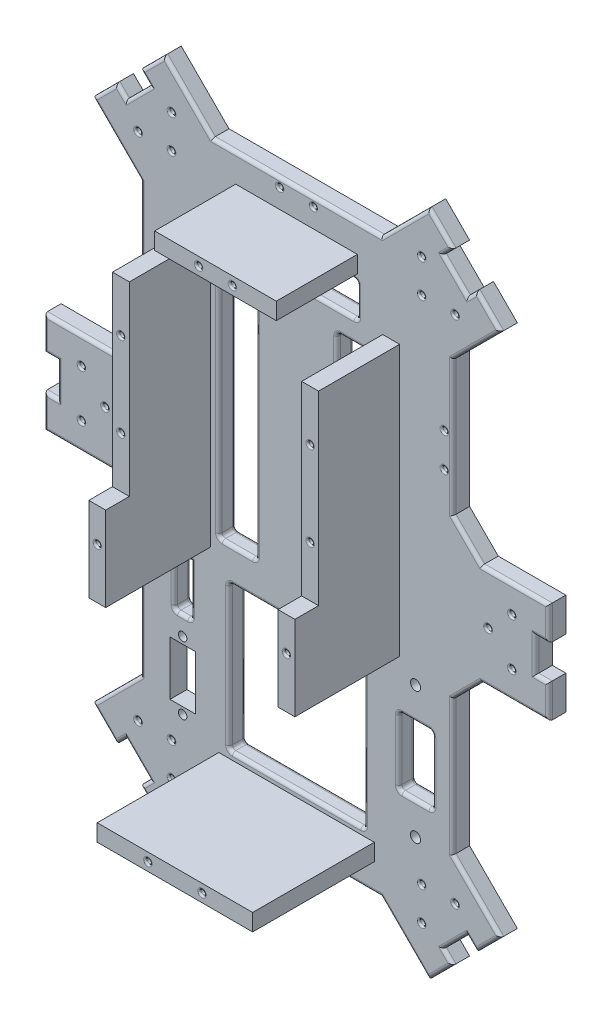
SolidWorks part; units mm, degrees
ref_plane "Płaszczyzna przednia" through (0, 0, 0) normal (0, 0, 1) x (1, 0, 0)
ref_plane "Płaszczyzna górna" through (0, 0, 0) normal (0, 1, 0) x (1, 0, 0)
ref_plane "Płaszczyzna prawa" through (0, 0, 0) normal (1, 0, 0) x (0, 0, -1)
sketch "Szkic1" plane through (0, 0, 0) normal (0, 0, 1) x (1, 0, 0)
  line L0 (0, 0) -> (-50, 0)
  line L1 (-50, 0) -> (-64.1421, 14.1421)
  line L2 (-64.1421, 14.1421) -> (-71.2132, 7.0711)
  line L3 (-71.2132, 7.0711) -> (-68.3848, 4.2426)
  line L4 (-68.3848, 4.2426) -> (-75.4558, -2.8284)
  line L5 (-75.4558, -2.8284) -> (-78.2843, 0)
  line L6 (-78.2843, 0) -> (-85.3553, -7.0711)
  line L7 (-85.3553, -7.0711) -> (-71.2132, -21.2132)
  line L8 (-71.2132, -21.2132) -> (-71.2132, -61.2132)
  line L9 (0, 0) -> (14.1421, 14.1421)
  line L10 (14.1421, 14.1421) -> (21.2132, 7.0711)
  line L11 (21.2132, 7.0711) -> (18.3848, 4.2426)
  line L12 (18.3848, 4.2426) -> (25.4558, -2.8284)
  line L13 (25.4558, -2.8284) -> (28.2843, 0)
  line L14 (28.2843, 0) -> (35.3553, -7.0711)
  line L15 (35.3553, -7.0711) -> (21.2132, -21.2132)
  line L16 (21.2132, -21.2132) -> (21.2132, -61.2132)
  line L17 (-71.2132, -61.2132) -> (-79.6985, -69.6985)
  line L18 (-79.6985, -69.6985) -> (-99.6985, -69.6985)
  line L19 (-99.6985, -69.6985) -> (-99.6985, -79.6985)
  line L20 (-99.6985, -79.6985) -> (-95.6985, -79.6985)
  line L21 (-95.6985, -79.6985) -> (-95.6985, -89.6985)
  line L22 (-95.6985, -89.6985) -> (-99.6985, -89.6985)
  line L23 (-99.6985, -89.6985) -> (-99.6985, -99.6985)
  line L24 (-99.6985, -99.6985) -> (-79.6985, -99.6985)
  line L25 (21.2132, -61.2132) -> (29.6985, -69.6985)
  line L26 (29.6985, -69.6985) -> (49.6985, -69.6985)
  line L27 (49.6985, -69.6985) -> (49.6985, -79.6985)
  line L28 (49.6985, -79.6985) -> (45.6985, -79.6985)
  line L29 (45.6985, -79.6985) -> (45.6985, -89.6985)
  line L30 (45.6985, -89.6985) -> (49.6985, -89.6985)
  line L31 (49.6985, -89.6985) -> (49.6985, -99.6985)
  line L32 (49.6985, -99.6985) -> (29.6985, -99.6985)
  line L33 (29.6985, -99.6985) -> (21.2132, -108.1838)
  line L34 (-79.6985, -99.6985) -> (-71.2132, -108.1838)
  line L35 (-71.2132, -108.1838) -> (-71.2132, -148.1838)
  line L36 (21.2132, -108.1838) -> (21.2132, -148.1838)
  line L37 (-71.2132, -148.1838) -> (-85.3553, -162.3259)
  line L38 (-85.3553, -162.3259) -> (-78.2843, -169.397)
  line L39 (-78.2843, -169.397) -> (-75.4558, -166.5685)
  line L40 (-75.4558, -166.5685) -> (-68.3848, -173.6396)
  line L41 (-68.3848, -173.6396) -> (-71.2132, -176.468)
  line L42 (-71.2132, -176.468) -> (-64.1421, -183.5391)
  line L43 (-64.1421, -183.5391) -> (-50, -169.397)
  line L44 (21.2132, -148.1838) -> (35.3553, -162.3259)
  line L45 (35.3553, -162.3259) -> (28.2843, -169.397)
  line L46 (28.2843, -169.397) -> (25.4558, -166.5685)
  line L47 (25.4558, -166.5685) -> (18.3848, -173.6396)
  line L48 (18.3848, -173.6396) -> (21.2132, -176.468)
  line L49 (21.2132, -176.468) -> (14.1421, -183.5391)
  line L50 (14.1421, -183.5391) -> (0, -169.397)
  line L51 (-50, -169.397) -> (0, -169.397)
  dimension "D1" = 225
  dimension "D2" = 225
  dimension "D3" = 20
  dimension "D4" = 20
  dimension "D5" = 10
  dimension "D6" = 4
  dimension "D7" = 50
  dimension "D8" = 10
  dimension "D9" = 10
  dimension "D10" = 20
  dimension "D11" = 4
  dimension "D12" = 10
  dimension "D13" = 4
  dimension "D14" = 10
  dimension "D15" = 4
  dimension "D16" = 10
  dimension "D17" = 20
  dimension "D18" = 225
  dimension "D19" = 40
  dimension "D20" = 12
  dimension "D21" = 20
  dimension "D22" = 10
  dimension "D23" = 4
  dimension "D24" = 10
  dimension "D25" = 4
  dimension "D26" = 10
  dimension "D27" = 20
  dimension "D29" = 12
  dimension "D30" = 20
  dimension "D31" = 10
  dimension "D32" = 4
  dimension "D33" = 10
  dimension "D34" = 4
  dimension "D35" = 10
  dimension "D36" = 20
  dimension "D37" = 12
  dimension "D38" = 12
  dimension "D39" = 40
  dimension "D40" = 40
  dimension "D41" = 20
  dimension "D42" = 10
  dimension "D43" = 4
  dimension "D44" = 10
  dimension "D45" = 4
  dimension "D46" = 10
  dimension "D47" = 20
  dimension "D48" = 20
  dimension "D49" = 10
  dimension "D50" = 4
  dimension "D51" = 10
  dimension "D52" = 4
  dimension "D53" = 10
  dimension "D54" = 20
  dimension "D55" = 135
  dimension "D56" = 90
  dimension "D57" = 270
  dimension "D58" = 225
  dimension "D59" = 225
  dimension "D60" = 135
extrude "Dodanie-wyciągnięcie1" add sketch "Szkic1" along normal blind 5 contours L36 L44 L45 L46 L47 L48 L49 L50 L51 L43 L42 L41 L40 L39 L38 L37 L35 L34 L24 L23 L22 L21 L20 L19 L18 L17 L8 L7 L6 L5 L4 L3 L2 L1 L0 L9 L10 L11 L12 L13 L14 L15 L16 L25 L26 L27 L28 L29 L30 L31 L32 L33
sketch "Szkic11" plane through (0, 0, 5) normal (0, 0, 1) x (1, 0, 0)
  line L0 (-79.6985, -69.6985) -> (-99.6985, -69.6985) construction
  line L1 (-85.3553, -7.0711) -> (-71.2132, -21.2132) construction
  line L2 (-99.6985, -69.6985) -> (-99.6985, -79.6985) construction
  line L3 (-99.6985, -99.6985) -> (-79.6985, -99.6985) construction
  line L4 (-78.2843, 0) -> (-85.3553, -7.0711) construction
  line L5 (-50, 0) -> (-64.1421, 14.1421) construction
  line L6 (-64.1421, 14.1421) -> (-71.2132, 7.0711) construction
  line L7 (14.1421, 14.1421) -> (21.2132, 7.0711) construction
  line L8 (35.3553, -7.0711) -> (21.2132, -21.2132) construction
  line L9 (28.2843, 0) -> (35.3553, -7.0711) construction
  line L10 (0, 0) -> (14.1421, 14.1421) construction
  line L11 (49.6985, -89.6985) -> (49.6985, -99.6985) construction
  line L12 (49.6985, -99.6985) -> (29.6985, -99.6985) construction
  line L13 (49.6985, -69.6985) -> (49.6985, -79.6985) construction
  line L14 (29.6985, -69.6985) -> (49.6985, -69.6985) construction
  line L15 (21.2132, -176.468) -> (14.1421, -183.5391) construction
  line L16 (14.1421, -183.5391) -> (0, -169.397) construction
  line L17 (35.3553, -162.3259) -> (28.2843, -169.397) construction
  line L18 (21.2132, -148.1838) -> (35.3553, -162.3259) construction
  line L19 (-85.3553, -162.3259) -> (-78.2843, -169.397) construction
  line L20 (-71.2132, -176.468) -> (-64.1421, -183.5391) construction
  line L21 (-64.1421, -183.5391) -> (-50, -169.397) construction
  line L22 (-71.2132, -148.1838) -> (-85.3553, -162.3259) construction
  line L23 (-99.6985, -89.6985) -> (-99.6985, -99.6985) construction
  circle A0 centre (-81.6985, -84.6985) radius 0.8
  circle A1 centre (-88.6985, -77.6985) radius 0.8
  circle A2 centre (-88.6985, -91.6985) radius 0.8
  circle A3 centre (-62.0208, -9.1924) radius 0.8
  circle A4 centre (-62.0208, 0.7071) radius 0.8
  circle A5 centre (-71.9203, -9.1924) radius 0.8
  circle A6 centre (12.0208, -9.1924) radius 0.8
  circle A7 centre (12.0208, 0.7071) radius 0.8
  circle A8 centre (21.9203, -9.1924) radius 0.8
  circle A9 centre (31.6985, -84.6985) radius 0.8
  circle A10 centre (38.6985, -77.6985) radius 0.8
  circle A11 centre (38.6985, -91.6985) radius 0.8
  circle A12 centre (12.0208, -160.2046) radius 0.8
  circle A13 centre (21.9203, -160.2046) radius 0.8
  circle A14 centre (12.0208, -170.1041) radius 0.8
  circle A15 centre (-62.0208, -160.2046) radius 0.8
  circle A16 centre (-71.9203, -160.2046) radius 0.8
  circle A17 centre (-62.0208, -170.1041) radius 0.8
  dimension "D1" = 1.6
  dimension "D4" = 1.6
  dimension "D5" = 1.6
  dimension "D10" = 1.6
  dimension "D11" = 1.6
  dimension "D12" = 1.6
  dimension "D19" = 1.6
  dimension "D20" = 1.6
  dimension "D21" = 1.6
  dimension "D30" = 1.6
  dimension "D31" = 1.6
  dimension "D32" = 1.6
  dimension "D41" = 1.6
  dimension "D42" = 1.6
  dimension "D43" = 1.6
  dimension "D50" = 1.6
  dimension "D51" = 1.6
  dimension "D52" = 1.6
  dimension "D2" = 15
  dimension "D3" = 18
  dimension "D6" = 7
  dimension "D7" = 7
  dimension "D8" = 8
  dimension "D9" = 8
  dimension "D13" = 18
  dimension "D14" = 15
  dimension "D15" = 8
  dimension "D16" = 8
  dimension "D17" = 11
  dimension "D18" = 11
  dimension "D22" = 18
  dimension "D23" = 15
  dimension "D24" = 11
  dimension "D25" = 11
  dimension "D26" = 8
  dimension "D27" = 8
  dimension "D28" = 14
  dimension "D29" = 14
  dimension "D33" = 18
  dimension "D34" = 15
  dimension "D35" = 11
  dimension "D36" = 11
  dimension "D37" = 8
  dimension "D38" = 8
  dimension "D39" = 14
  dimension "D40" = 7
  dimension "D44" = 18
  dimension "D45" = 15
  dimension "D46" = 11
  dimension "D47" = 11
  dimension "D48" = 8
  dimension "D49" = 8
  dimension "D53" = 18
  dimension "D54" = 11
  dimension "D55" = 11
  dimension "D56" = 8
  dimension "D57" = 15
  dimension "D58" = 8
  dimension "D59" = 14
  dimension "D60" = 14
  dimension "D61" = 14
  dimension "D62" = 11
  dimension "D63" = 11
extrude "Wytnij-wyciągnięcie7" cut sketch "Szkic11" against normal blind 60 and the other way blind 42
sketch "Szkic12" plane through (0, 0, 5) normal (0, 0, 1) x (1, 0, 0)
  line L0 (0, 0) -> (-50, 0) construction
  line L1 (-71.2132, -21.2132) -> (-71.2132, -61.2132) construction
  line L2 (-50, -169.397) -> (0, -169.397) construction
  line L3 (21.2132, -21.2132) -> (21.2132, -61.2132) construction
  circle A0 centre (-30, -2.5) radius 0.75
  circle A1 centre (-20, -2.5) radius 0.75
  circle A2 centre (-30, -166.897) radius 0.75
  circle A3 centre (-20, -166.897) radius 0.75
  circle A4 centre (-68.7132, -40.5) radius 0.75
  circle A5 centre (-68.7132, -50.5) radius 0.75
  circle A6 centre (18.7132, -40.5) radius 0.75
  circle A7 centre (18.7132, -50.5) radius 0.75
  dimension "D2" = 1.5
  dimension "D3" = 1.5
  dimension "D8" = 1.5
  dimension "D9" = 1.5
  dimension "D15" = 1.5
  dimension "D16" = 1.5
  dimension "D17" = 1.5
  dimension "D18" = 1.5
  dimension "D1" = 2.5
  dimension "D4" = 2.5
  dimension "D5" = 20
  dimension "D6" = 10
  dimension "D7" = 20
  dimension "D10" = 2.5
  dimension "D11" = 2.5
  dimension "D12" = 20
  dimension "D13" = 10
  dimension "D14" = 20
  dimension "D19" = 2.5
  dimension "D20" = 2.5
  dimension "D21" = 2.5
  dimension "D22" = 2.5
  dimension "D23" = 40.5
  dimension "D24" = 50.5
  dimension "D25" = 40.5
  dimension "D26" = 50.5
extrude "Wytnij-wyciągnięcie8" cut sketch "Szkic12" against normal blind 66 and the other way blind 36
sketch "Szkic13" plane through (0, 0, 0) normal (0, 0, 1) x (1, 0, 0)
  line L0 (0, 0) -> (-50, 0) construction
  line L1 (-47.9982, -31.5) -> (-36.9982, -31.5)
  line L2 (-47.9982, -31.5) -> (-47.9982, -101.5)
  line L3 (-47.9982, -101.5) -> (-36.9982, -101.5)
  line L4 (-36.9982, -31.5) -> (-36.9982, -101.5)
  line L5 (-2.0018, -31.5) -> (-13.0018, -31.5)
  line L6 (-2.0018, -31.5) -> (-2.0018, -101.5)
  line L7 (-2.0018, -101.5) -> (-13.0018, -101.5)
  line L8 (-13.0018, -31.5) -> (-13.0018, -101.5)
  line L9 (-71.2132, -21.2132) -> (-71.2132, -61.2132) construction
  line L10 (21.2132, -21.2132) -> (21.2132, -61.2132) construction
  line L11 (-71.2132, -108.1838) -> (-71.2132, -148.1838) construction
  line L12 (-45.0032, -111.497) -> (-5.0032, -111.497)
  line L13 (-45.0032, -111.497) -> (-45.0032, -154.397)
  line L14 (-45.0032, -154.397) -> (-5.0032, -154.397)
  line L15 (-5.0032, -111.497) -> (-5.0032, -154.397)
  line L16 (21.2132, -108.1838) -> (21.2132, -148.1838) construction
  line L17 (-50, -169.397) -> (0, -169.397) construction
  line L19 (-61.2132, -111.497) -> (-56.2132, -111.497)
  line L20 (-61.2132, -111.497) -> (-61.2132, -126.497)
  line L21 (-61.2132, -126.497) -> (-56.2132, -126.497)
  line L22 (-56.2132, -111.497) -> (-56.2132, -126.497)
  line L23 (-62.4632, -133.997) -> (-54.9632, -133.997)
  line L24 (-62.4632, -133.997) -> (-62.4632, -149.997)
  line L25 (-62.4632, -149.997) -> (-54.9632, -149.997)
  line L26 (-54.9632, -133.997) -> (-54.9632, -149.997)
  line L31 (5.2132, -119.5) -> (15.2132, -119.5)
  line L32 (5.2132, -119.5) -> (5.2132, -139.5)
  line L33 (5.2132, -139.5) -> (15.2132, -139.5)
  line L34 (15.2132, -119.5) -> (15.2132, -139.5)
  line L35 (-43.0032, -15) -> (-7.0032, -15)
  line L36 (-43.0032, -15) -> (-43.0032, -25)
  line L37 (-43.0032, -25) -> (-7.0032, -25)
  line L38 (-7.0032, -15) -> (-7.0032, -25)
  circle A0 centre (10.2132, -110) radius 1.5
  circle A1 centre (10.2132, -149) radius 1.5
  circle A2 centre (-58.7132, -131.997) radius 1.25
  circle A3 centre (-58.7132, -151.997) radius 1.25
  dimension "D39" = 3
  dimension "D40" = 3
  dimension "D30" = 2.5
  dimension "D41" = 2.5
  dimension "D1" = 70
  dimension "D2" = 31.5
  dimension "D3" = 23.215
  dimension "D4" = 11
  dimension "D5" = 11
  dimension "D6" = 31.5
  dimension "D7" = 70
  dimension "D8" = 23.215
  dimension "D9" = 40
  dimension "D10" = 26.21
  dimension "D11" = 26.2164
  dimension "D12" = 42.9
  dimension "D13" = 15
  dimension "D14" = 9.5
  dimension "D15" = 10
  dimension "D16" = 5
  dimension "D17" = 9.997
  dimension "D18" = 15
  dimension "D19" = 8.75
  dimension "D20" = 7.5
  dimension "D21" = 7.5
  dimension "D22" = 16
  dimension "D23" = 18
  dimension "D24" = 10
  dimension "D25" = 45.9964
  dimension "D26" = 3.75
  dimension "D27" = 3.75
  dimension "D28" = 6
  dimension "D29" = 20
  dimension "D31" = 10.2164
  dimension "D32" = 28.21
  dimension "D33" = 36
  dimension "D34" = 28.2164
  dimension "D35" = 10
  dimension "D36" = 15
  dimension "D37" = 5
  dimension "D38" = 5
  dimension "50" = 39
  dimension "D42" = 2
  dimension "D43" = 2
extrude "Wytnij-wyciągnięcie9" cut sketch "Szkic13" against normal blind 47 and the other way blind 54
sketch "Szkic14" plane through (0, 0, 5) normal (0, 0, 1) x (1, 0, 0)
  line L0 (-50.4982, -25) -> (-55.4982, -25)
  line L1 (-55.4982, -25) -> (-55.4982, -105)
  line L2 (-55.4982, -105) -> (-50.4982, -105)
  line L3 (-50.4982, -105) -> (-50.4982, -25)
  line L4 (5.5018, -25) -> (5.5018, -105)
  line L5 (5.5018, -105) -> (0.5018, -105)
  line L6 (0.5018, -25) -> (5.5018, -25)
  line L7 (0.5018, -105) -> (0.5018, -25)
  line L8 (-47.9982, -101.5) -> (-47.9982, -31.5) construction
  line L9 (-2.0018, -31.5) -> (-2.0018, -101.5) construction
  line L10 (-5.0032, -154.397) -> (-45.0032, -154.397) construction
  line L11 (0, 0) -> (-50, 0) construction
  line L13 (-48.0032, -156.397) -> (-2.0032, -156.397)
  line L14 (-2.0032, -156.397) -> (-2.0032, -161.397)
  line L15 (-2.0032, -161.397) -> (-48.0032, -161.397)
  line L16 (-48.0032, -161.397) -> (-48.0032, -156.397)
  line L18 (-71.2132, -108.1838) -> (-71.2132, -148.1838) construction
  line L19 (-43.0032, -13.197) -> (-7.0032, -13.197)
  line L20 (-7.0032, -13.197) -> (-7.0032, -8.197)
  line L21 (-7.0032, -8.197) -> (-43.0032, -8.197)
  line L22 (-43.0032, -8.197) -> (-43.0032, -13.197)
  line L24 (-71.2132, -21.2132) -> (-71.2132, -61.2132) construction
  circle A0 centre (-30.0032, -10.697) radius 0.75
  circle A1 centre (-20.0032, -10.697) radius 0.75
  circle A2 centre (-33.0032, -158.897) radius 0.75
  circle A3 centre (-17.0032, -158.897) radius 0.75
  circle A4 centre (-52.9982, -40) radius 0.75
  circle A5 centre (-52.9982, -65) radius 0.75
  circle A6 centre (-52.9982, -90) radius 0.75
  circle A7 centre (3.0018, -40) radius 0.75
  circle A8 centre (3.0018, -65) radius 0.75
  circle A9 centre (3.0018, -90) radius 0.75
  dimension "D21" = 1.5
  dimension "D22" = 1.5
  dimension "D26" = 1.5
  dimension "D27" = 1.5
  dimension "D33" = 1.5
  dimension "D34" = 1.5
  dimension "D35" = 1.5
  dimension "D42" = 1.5
  dimension "D43" = 1.5
  dimension "D44" = 1.5
  dimension "D1" = 80
  dimension "D2" = 5
  dimension "D3" = 5
  dimension "D4" = 80
  dimension "D5" = 51
  dimension "D6" = 2.5
  dimension "D7" = 2.5036
  dimension "D8" = 25
  dimension "D9" = 25
  dimension "D10" = 5
  dimension "D11" = 2
  dimension "D12" = 46
  dimension "D13" = 23.21
  dimension "D14" = 143.2
  dimension "D15" = 5
  dimension "D16" = 28.21
  dimension "D17" = 36
  dimension "D18" = 2.5
  dimension "D19" = 2.5
  dimension "D20" = 10
  dimension "D23" = 13
  dimension "D24" = 2.5
  dimension "D25" = 2.5
  dimension "D28" = 16
  dimension "D29" = 15
  dimension "D30" = 2.5
  dimension "D31" = 2.5
  dimension "D32" = 2.5
  dimension "D36" = 25
  dimension "D37" = 25
  dimension "D38" = 15
  dimension "D39" = 2.5
  dimension "D40" = 2.5
  dimension "D41" = 2.5
  dimension "D45" = 15
  dimension "D46" = 25
  dimension "D47" = 25
extrude "Dodanie-wyciągnięcie7" add sketch "Szkic14" along normal blind 24
extrude "Dodanie-wyciągnięcie8" add sketch "Szkic14<9>" along normal blind 36 contours L16 L15 L14 L13 A3 A2 region at (-25.0032, -158.897, 5)
sketch "Szkic14<9>" plane through (0, 0, 5) normal (0, 0, 1) x (1, 0, 0) same geometry as "Szkic14"
sketch "Szkic17" plane through (0, 0, 0) normal (0, 0, 1) x (1, 0, 0)
  line L0 (-50.4982, -80) -> (-55.4982, -80)
  line L1 (-50.4982, -105) -> (-50.4982, -25) construction
  line L2 (-55.4982, -25) -> (-55.4982, -105) construction
  line L3 (-55.4982, -80) -> (-55.4982, -105)
  line L4 (-55.4982, -105) -> (-50.4982, -105)
  line L5 (-50.4982, -105) -> (-50.4982, -80)
  line L6 (0.5018, -105) -> (5.5018, -105)
  line L7 (5.5018, -105) -> (5.5018, -80)
  line L8 (5.5018, -105) -> (5.5018, -25) construction
  line L9 (5.5018, -80) -> (0.5018, -80)
  line L10 (0.5018, -25) -> (0.5018, -105) construction
  line L11 (0.5018, -80) -> (0.5018, -105)
  circle A0 centre (-52.9982, -90) radius 0.75
  circle A1 centre (3.0018, -90) radius 0.75
  dimension "D3" = 1.5
  dimension "D4" = 1.5
  dimension "D1" = 25
  dimension "D2" = 25
extrude "Dodanie-wyciągnięcie9" add sketch "Szkic17" along normal blind 36
fillet "Zaokrąglenie3" radius 1 52 edges at (-97.6985, -79.6985, 5) (-95.6985, -84.6985, 5) (-97.6985, -89.6985, 5) (-99.6985, -94.6985, 5) (-89.6985, -99.6985, 5) (-75.4558, -103.9411, 5) (-71.2132, -128.1838, 5) (-78.2843, -155.2548, 5) (-76.8701, -167.9828, 5) (-69.799, -175.0538, 5) (-81.8198, -165.8614, 5) (-71.9203, -170.1041, 5) (-67.6777, -180.0036, 5) (-57.0711, -176.468, 5) (-25, -169.397, 5) (7.0711, -176.468, 5) (17.6777, -180.0036, 5) (19.799, -175.0538, 5) (21.9203, -170.1041, 5) (26.8701, -167.9828, 5) (31.8198, -165.8614, 5) (28.2843, -155.2548, 5) (21.2132, -128.1838, 5) (25.4558, -103.9411, 5) (39.6985, -99.6985, 5) (49.6985, -94.6985, 5) (47.6985, -89.6985, 5) (45.6985, -84.6985, 5) (47.6985, -79.6985, 5) (49.6985, -74.6985, 5) (39.6985, -69.6985, 5) (25.4558, -65.4558, 5) (21.2132, -41.2132, 5) (28.2843, -14.1421, 5) (31.8198, -3.5355, 5) (26.8701, -1.4142, 5) (21.9203, 0.7071, 5) (19.799, 5.6569, 5) (17.6777, 10.6066, 5) (7.0711, 7.0711, 5) (-25, 0, 5) (-69.799, 5.6569, 5) (-67.6777, 10.6066, 5) (-57.0711, 7.0711, 5) (-71.9203, 0.7071, 5) (-76.8701, -1.4142, 5) (-81.8198, -3.5355, 5) (-78.2843, -14.1421, 5) (-71.2132, -41.2132, 5) (-75.4558, -65.4558, 5) (-89.6985, -69.6985, 5) (-99.6985, -74.6985, 5)
fillet "Zaokrąglenie4" radius 1 70 edges at (-56.2132, -118.997, 5) (-61.2132, -118.997, 5) (-61.2132, -118.997, 0) (-56.2132, -118.997, 0) (-45.0032, -132.947, 5) (-5.0032, -132.947, 5) (-5.0032, -132.947, 0) (-45.0032, -132.947, 0) (-13.0018, -66.5, 5) (-2.0018, -66.5, 5) (-2.0018, -66.5, 0) (-13.0018, -66.5, 0) (-47.9982, -66.5, 5) (-36.9982, -66.5, 5) (-36.9982, -66.5, 0) (-47.9982, -66.5, 0) (-7.0032, -20, 5) (-43.0032, -20, 5) (-43.0032, -20, 0) (-7.0032, -20, 0) (-58.7132, -126.497, 5) (-61.2132, -126.497, 2.5) (-58.7132, -126.497, 0) (-56.2132, -126.497, 2.5) (-25.0032, -154.397, 5) (-45.0032, -154.397, 2.5) (-25.0032, -154.397, 0) (-5.0032, -154.397, 2.5) (-25.0032, -111.497, 5) (-5.0032, -111.497, 2.5) (-25.0032, -111.497, 0) (-45.0032, -111.497, 2.5) (-7.5018, -101.5, 5) (-13.0018, -101.5, 2.5) (-7.5018, -101.5, 0) (-2.0018, -101.5, 2.5) (-7.5018, -31.5, 5) (-2.0018, -31.5, 2.5) (-7.5018, -31.5, 0) (-13.0018, -31.5, 2.5) (-42.4982, -101.5, 5) (-47.9982, -101.5, 2.5) (-42.4982, -101.5, 0) (-36.9982, -101.5, 2.5) (-42.4982, -31.5, 5) (-36.9982, -31.5, 2.5) (-42.4982, -31.5, 0) (-47.9982, -31.5, 2.5) (-25.0032, -15, 5) (-7.0032, -15, 2.5) (-25.0032, -15, 0) (-43.0032, -15, 2.5) (-25.0032, -25, 5) (-43.0032, -25, 2.5) (-25.0032, -25, 0) (-7.0032, -25, 2.5) (-58.7132, -111.497, 0) (-58.7132, -111.497, 5) (10.2132, -139.5, 5) (10.2132, -119.5, 5) (10.2132, -119.5, 0) (10.2132, -139.5, 0) (15.2132, -129.5, 5) (15.2132, -139.5, 2.5) (15.2132, -129.5, 0) (15.2132, -119.5, 2.5) (5.2132, -129.5, 5) (5.2132, -119.5, 2.5) (5.2132, -129.5, 0) (5.2132, -139.5, 2.5)
fillet "Zaokrąglenie5" radius 0.5 36 edges at (12.8208, -170.1041, 5) (12.8208, -160.2046, 5) (22.7203, -160.2046, 5) (-19.25, -166.897, 5) (-29.25, -166.897, 5) (-61.2208, -170.1041, 5) (-61.2208, -160.2046, 5) (-71.1203, -160.2046, 5) (-67.9632, -50.5, 5) (-67.9632, -40.5, 5) (39.4985, -91.6985, 5) (32.4985, -84.6985, 5) (39.4985, -77.6985, 5) (19.4632, -50.5, 5) (19.4632, -40.5, 5) (22.7203, -9.1924, 5) (12.8208, -9.1924, 5) (-29.25, -2.5, 5) (-19.25, -2.5, 5) (12.8208, 0.7071, 5) (-61.2208, -9.1924, 5) (-71.1203, -9.1924, 5) (-61.2208, 0.7071, 5) (-87.8985, -91.6985, 5) (-80.8985, -84.6985, 5) (-87.8985, -77.6985, 5) (-19.2532, -10.697, 29) (-29.2532, -10.697, 29) (-32.2532, -158.897, 41) (-16.2532, -158.897, 41) (3.7518, -90, 36) (3.7518, -65, 29) (3.7518, -40, 29) (-52.2482, -90, 36) (-52.2482, -65, 29) (-52.2482, -40, 29)
